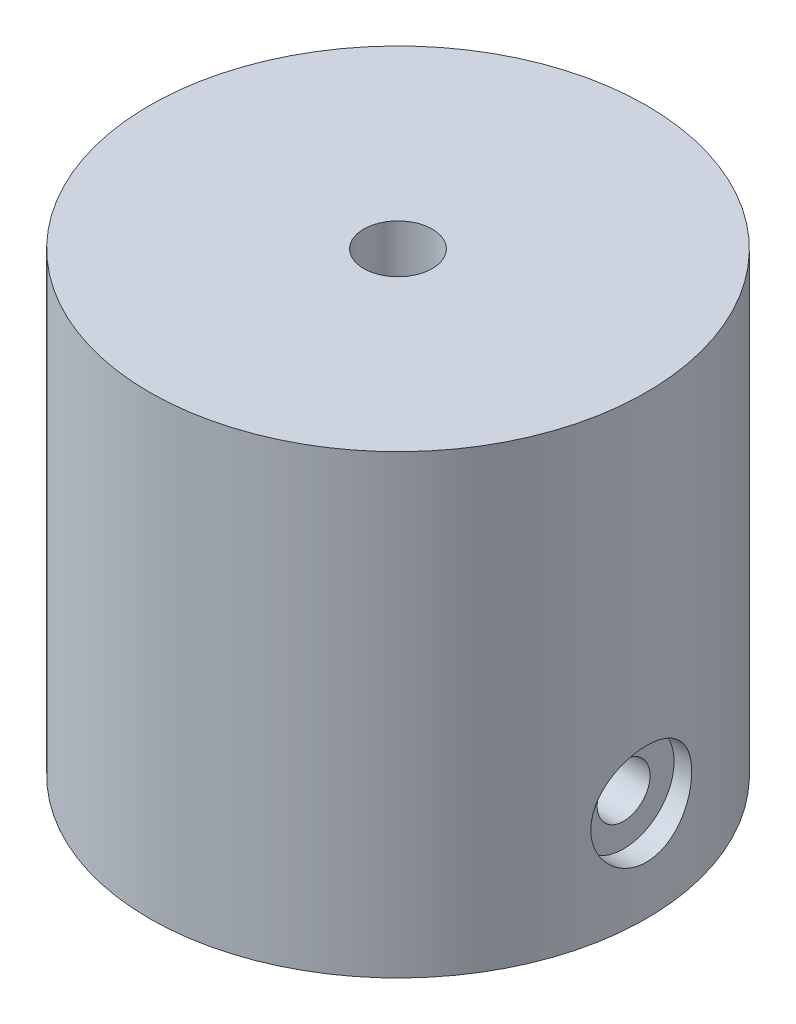
SolidWorks part; units mm, degrees
ref_plane "Front Plane" through (0, 0, 0) normal (0, 0, 1) x (1, 0, 0)
ref_plane "Top Plane" through (0, 0, 0) normal (0, 1, 0) x (1, 0, 0)
ref_plane "Right Plane" through (0, 0, 0) normal (1, 0, 0) x (0, 0, -1)
sketch "Sketch1" plane through (0, 0, 0) normal (0, 1, 0) x (1, 0, 0)
  circle A0 centre (0, 0) radius 12.7
  dimension "D1" = 25.4
extrude "Boss-Extrude1" add sketch "Sketch1" along normal blind 23.3
hole_wizard "Ø3.0mm Dowel Hole2" positions "Sketch2" profile "Sketch3" hole size "Ø3.0" standard "ANSI Metric" end condition through all
sketch "Sketch2" plane through (0, 23.3, 0) normal (0, 1, 0) x (1, 0, 0)
  point P0 (0, 0)
sketch "Sketch3" plane through (0, 23.3, 0) normal (1, 0, 0) x (0, 0, 1)
  line L0 (0, 0) -> (0, 23.3)
  line L1 (0, 23.3) -> (1.75, 23.3)
  line L2 (1.75, 23.3) -> (1.75, 0)
  line L5 (1.75, 0) -> (0, 0)
  line L11 (0, -6.35) -> (0, 107.95) construction
  dimension "Thru Hole Dia." = 3.5
  dimension "Thru Hole Depth" = 23.3
sketch "Sketch4" plane through (0, 0, 0) normal (1, 0, 0) x (0, 0, -1)
  line L0 (-12.7, 23.3) -> (-12.7, 0) construction
  line L1 (-12.7, 20.125) -> (-8.89, 20.125)
  line L2 (-12.7, 20.125) -> (-12.7, 3.175)
  line L3 (-12.7, 3.175) -> (-8.89, 3.175)
  line L4 (-8.89, 20.125) -> (-8.89, 3.175)
  line L5 (-12.7, 0) -> (12.7, 0) construction
  line L6 (12.7, 23.3) -> (-12.7, 23.3) construction
  line L7 (0, 0) -> (0, 26.8631) construction
  dimension "D1" = 3.175
  dimension "D2" = 3.175
  dimension "D3" = 3.81
ref_plane "Plane1" through (12.7, 0, 0) normal (1, 0, 0) x (0, 0, -1)
sketch "Sketch5" plane through (12.7, 0, 0) normal (1, 0, 0) x (0, 0, -1)
  line L0 (1.75, 23.3) -> (-1.75, 23.3) construction
  circle A0 centre (0, 18.22) radius 1.27
  circle A1 centre (0, 5.08) radius 1.27
  dimension "D3" = 2.54
  dimension "D1" = 5.08
  dimension "D2" = 5.08
hole_wizard "CBORE for #2 Button Head Cap Screw1" positions "Sketch6" profile "Sketch7" counterbore size "#2" standard "ANSI Inch" end condition up to next
sketch "Sketch6" plane through (12.7, 0, 0) normal (1, 0, 0) x (0, 0, -1)
  point P3 (0, 5.08)
  point P7 (0, 0)
sketch "Sketch7" plane through (12.7, 5.08, 0) normal (0, 1, 0) x (0, 0, -1)
  line L0 (0, 0) -> (0, 10.95)
  line L1 (0, 10.95) -> (1.3525, 10.95)
  line L3 (1.3525, 10.95) -> (1.3526, 1.1684)
  line L4 (1.3526, 1.1684) -> (2.5794, 1.1684)
  line L5 (2.5794, 1.1684) -> (2.5794, 0)
  line L7 (2.5794, 0) -> (0, 0)
  line L11 (0, -6.35) -> (0, 107.95) construction
  dimension "Thru Hole Dia." = 2.7051
  dimension "Thru Hole Depth" = 10.95
  dimension "C'Bore Dia." = 5.1587
  dimension "C'Bore Depth" = 1.1684
sketch "Sketch8" plane through (0, 0, 0) normal (0, -1, 0) x (1, 0, 0)
  circle A0 centre (0, 0) radius 2.75
  circle A1 centre (0, 0) radius 11.2
  circle A2 centre (0, 0) radius 1.75 construction
  circle A3 centre (0, 0) radius 12.7 construction
  dimension "D1" = 1
  dimension "D2" = 1.5
extrude "Cut-Extrude1" cut sketch "Sketch8" against normal blind 2.54
